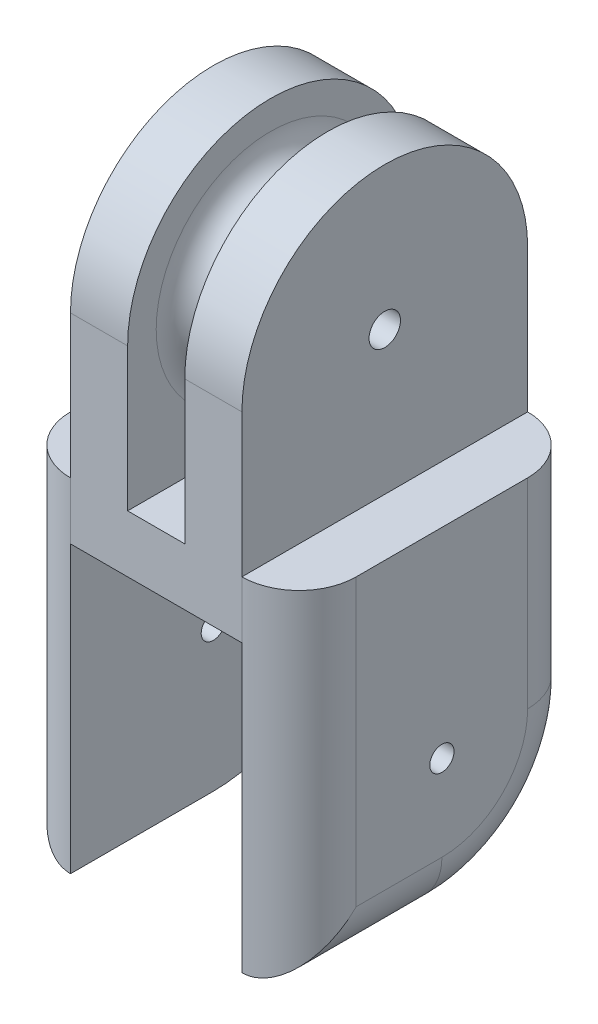
SolidWorks part; units mm, degrees
ref_plane "Front Plane" through (0, 0, 0) normal (0, 0, 1) x (1, 0, 0)
ref_plane "Top Plane" through (0, 0, 0) normal (0, 1, 0) x (1, 0, 0)
ref_plane "Right Plane" through (0, 0, 0) normal (1, 0, 0) x (0, 0, -1)
sketch "Sketch1" plane through (0, 0, 0) normal (0, 1, 0) x (1, 0, 0)
  line L0 (10, 10) -> (-10, -10) construction
  line L1 (-10, 10) -> (10, 10)
  line L2 (-10, 10) -> (-10, -10)
  line L3 (-10, -10) -> (10, -10)
  line L4 (10, 10) -> (10, -10)
  line L5 (-10, 10) -> (10, -10) construction
  point P5 (0, 0)
  dimension "D1" = 20
  dimension "D2" = 20
extrude "Boss-Extrude1" add sketch "Sketch1" along normal blind 4
sketch "Sketch4" plane through (0, 0, 0) normal (0, -1, 0) x (1, 0, 0)
  line L0 (10, -10) -> (-10, -10) construction
  line L1 (-10, 10) -> (-6, 10)
  line L2 (-10, 10) -> (-10, -10)
  line L3 (-10, -10) -> (-6, -10)
  line L4 (-6, 10) -> (-6, -10)
  line L5 (-10, 10) -> (10, 10) construction
  line L6 (10, -10) -> (6, -10)
  line L7 (10, -10) -> (10, 10)
  line L8 (10, 10) -> (6, 10)
  line L9 (6, -10) -> (6, 10)
  dimension "D1" = 4
  dimension "D2" = 4
extrude "Boss-Extrude2" add sketch "Sketch4" along normal blind 10
sketch "Sketch5" plane through (-10, 0, 0) normal (-1, 0, 0) x (0, 0, 1)
  line L0 (10, -10) -> (-10, -10) construction
  line L4 (0, -20) -> (10, -20)
  line L5 (10, -10) -> (10, -20)
  arc A0 (10, -10) -> (0, -20) centre (0, -10) ccw
extrude "Boss-Extrude3" add sketch "Sketch5" against normal blind 4
sketch "Sketch6" plane through (10, 0, 0) normal (1, 0, 0) x (0, 0, -1)
  line L0 (10, -10) -> (-10, -10) construction
  line L4 (0, -20) -> (-10, -20)
  line L5 (-10, -10) -> (-10, -20)
  arc A0 (0, -20) -> (-10, -10) centre (0, -10) ccw
extrude "Boss-Extrude4" add sketch "Sketch6" against normal blind 4
sketch "Sketch7" plane through (-10, 0, 0) normal (-1, 0, 0) x (0, 0, 1)
  circle A0 centre (0, -10) radius 0.85
  dimension "D1" = 1.7
extrude "Cut-Extrude1" cut sketch "Sketch7" against normal through all
fillet "Fillet1" radius 4 8 edges at (-10, -8, 10) (-10, -17.0711, -7.0711) (10, -8, 10) (10, -17.0711, -7.0711) (-10, -3, -10) (10, -3, -10) (10, -20, 5) (-10, -20, 5)
sketch "Sketch8" plane through (0, 4, 0) normal (0, 1, 0) x (1, 0, 0)
  line L0 (6, 10) -> (-6, 10) construction
  line L1 (6, -10) -> (2, -10)
  line L2 (6, -10) -> (6, 10)
  line L3 (6, 10) -> (2, 10)
  line L4 (2, -10) -> (2, 10)
  line L5 (-10, 6) -> (-10, -6) construction
  line L6 (-6, -10) -> (-2, -10)
  line L7 (-6, -10) -> (-6, 10)
  line L8 (-6, 10) -> (-2, 10)
  line L9 (-2, -10) -> (-2, 10)
  line L10 (10, -6) -> (10, 6) construction
  dimension "D1" = 4
  dimension "D2" = 4
  dimension "D3" = 4
  dimension "D4" = 4
extrude "Boss-Extrude5" add sketch "Sketch8" along normal blind 10
sketch "Sketch9" plane through (6, 0, 0) normal (1, 0, 0) x (0, 0, -1)
  line L0 (-10, 14) -> (10, 14) construction
  circle A0 centre (0, 14) radius 10
extrude "Boss-Extrude6" add sketch "Sketch9" against normal blind 4
sketch "Sketch10" plane through (-6, 0, 0) normal (-1, 0, 0) x (0, 0, 1)
  line L0 (-10, 14) -> (10, 14) construction
  circle A0 centre (0, 14) radius 10
extrude "Boss-Extrude7" add sketch "Sketch10" against normal blind 4
sketch "Sketch12" plane through (-6, 0, 0) normal (-1, 0, 0) x (0, 0, 1)
  circle A0 centre (0, 14) radius 1.1
  dimension "D1" = 2.2
extrude "Cut-Extrude2" cut sketch "Sketch12" against normal through all
sketch "Sketch13" plane through (-2, 0, 0) normal (1, 0, 0) x (0, 0, -1)
  circle A0 centre (0, 14) radius 6
  dimension "D1" = 12
sketch "Sketch14" plane through (-2, 0, 0) normal (1, 0, 0) x (0, 0, -1)
  circle A0 centre (0, 14) radius 1.1
  dimension "D1" = 2.2
extrude "Boss-Extrude8" add sketch "Sketch13" along normal blind 4
extrude "Cut-Extrude3" cut sketch "Sketch14" along normal blind 4
fillet "Fillet2" radius 2 2 edges at (2, 14, -6) (-2, 14, 6)
sketch "Sketch16" plane through (0, 0, 0) normal (0, -1, 0) x (1, 0, 0)
  line L0 (6, -10) -> (-6, -10) construction
  line L1 (-6, 0) -> (6, 0) construction
  line L2 (-6, -10) -> (-6, 10) construction
  line L3 (6, 10) -> (6, -10) construction
  circle A0 centre (0, -6) radius 0.5
  circle A1 centre (0, 6) radius 0.5
  dimension "D1" = 1
  dimension "D2" = 4
extrude "Cut-Extrude4" cut sketch "Sketch16" against normal up to next
